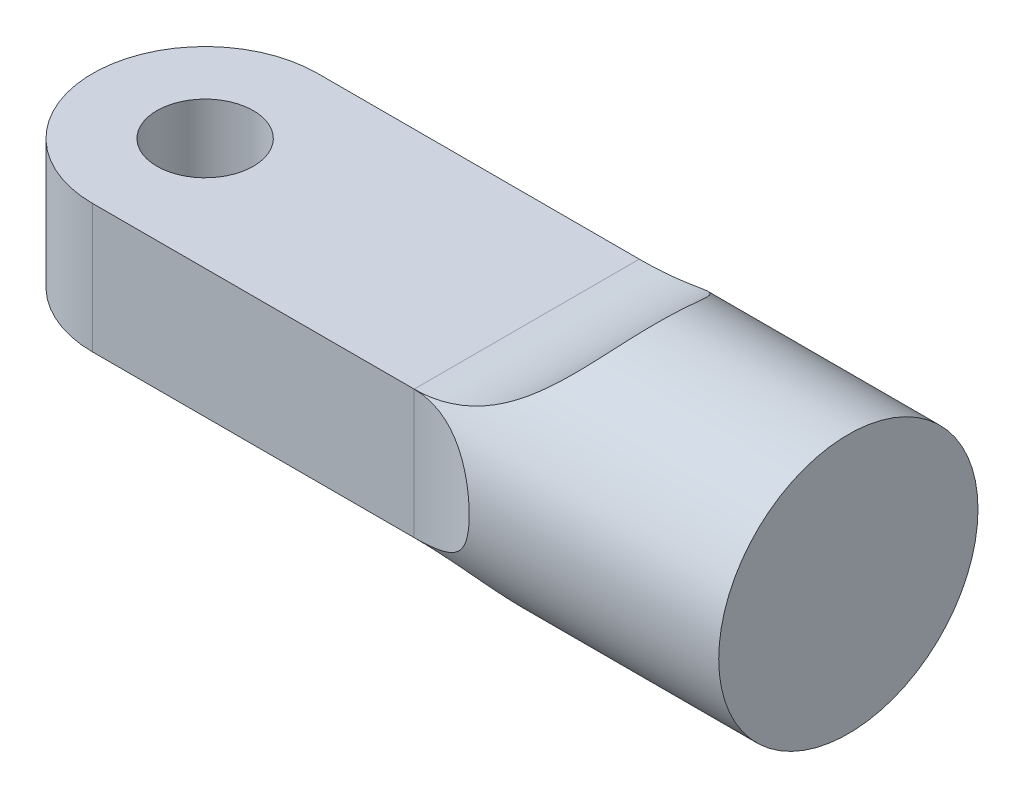
SolidWorks part; units mm, degrees
ref_plane "Front Plane" through (0, 0, 0) normal (0, 0, 1) x (1, 0, 0)
ref_plane "Top Plane" through (0, 0, 0) normal (0, 1, 0) x (1, 0, 0)
ref_plane "Right Plane" through (0, 0, 0) normal (1, 0, 0) x (0, 0, -1)
sketch "Sketch2" plane through (0, 0, 0) normal (0, 1, 0) x (1, 0, 0)
  line L0 (0, 0) -> (200, 0) construction
  line L1 (0, 35) -> (200, 35)
  line L2 (0, -35) -> (200, -35)
  line L3 (-35, 0) -> (0, 0) construction
  line L4 (200, -35) -> (200, 35)
  arc A1 (0, 35) -> (0, -35) centre (0, 0) ccw
  arc A2 (200, -35) -> (200, 35) centre (200, 0) ccw construction
  circle A3 centre (0, 0) radius 15
  point P3 (100, 0)
  dimension "D1" = 30
  dimension "D2" = 70
  dimension "D3" = 200
extrude "Boss-Extrude1" add sketch "Sketch2" along normal mid plane 40 contours L1 A1 L2 L4 A3 region at (90.1218, 0, 0)
sketch "Sketch3" plane through (200, 0, 0) normal (1, 0, 0) x (0, 0, -1)
  circle A0 centre (0, 0) radius 40.3113
extrude "Boss-Extrude2" add sketch "Sketch3" against normal blind 50
fillet "Fillet1" radius 50 2 edges at (150, 0, -35) (150, 0, 35)
fillet "Fillet2" radius 50 2 edges at (150, -20, 0) (150, 20, 0)
